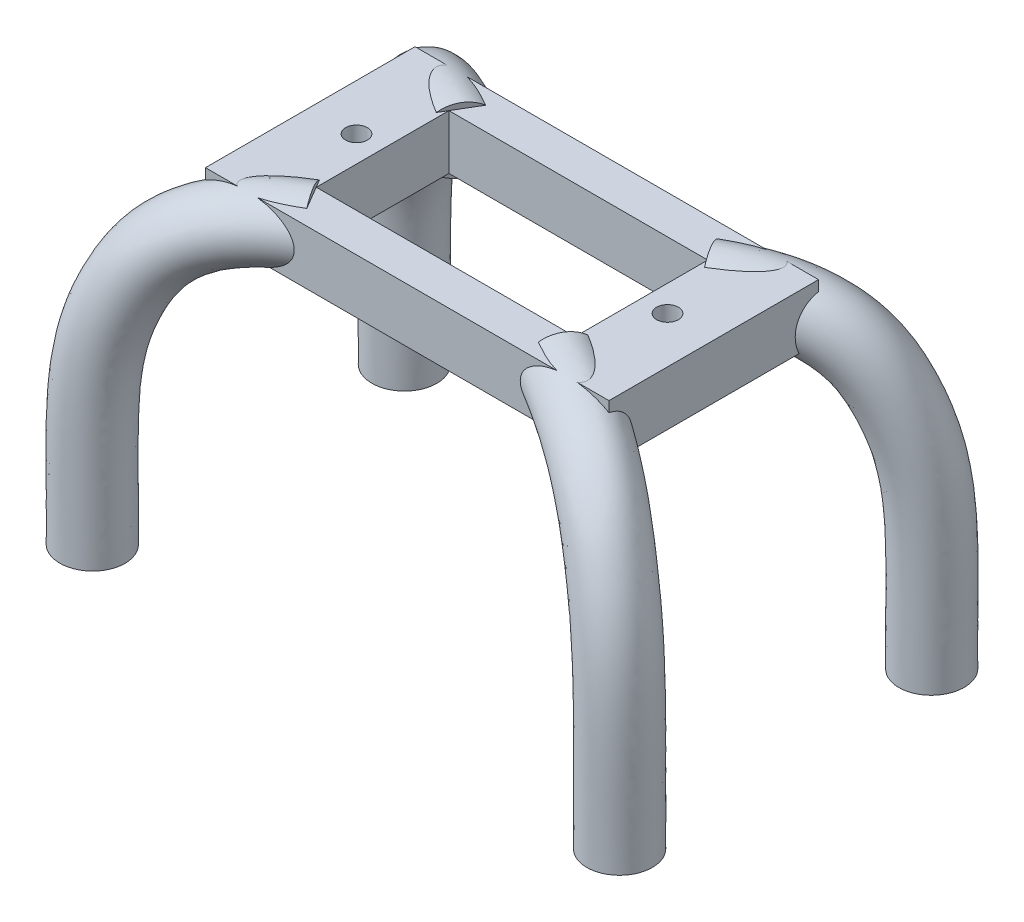
SolidWorks part; units mm, degrees
ref_plane "前视基准面" through (0, 0, 0) normal (0, 0, 1) x (1, 0, 0)
ref_plane "上视基准面" through (0, 0, 0) normal (0, 1, 0) x (1, 0, 0)
ref_plane "右视基准面" through (0, 0, 0) normal (1, 0, 0) x (0, 0, -1)
sketch "草图1" plane through (0, 0, 0) normal (0, 1, 0) x (1, 0, 0)
  line L0 (-5.8, 0) -> (-5.8, 12.535) construction
  line L1 (6.1, -6.1) -> (-17.7, -6.1)
  line L2 (6.1, -6.1) -> (6.1, 6.1)
  line L3 (6.1, 6.1) -> (-17.7, 6.1)
  line L4 (-17.7, -6.1) -> (-17.7, 6.1)
  line L5 (6.1, -6.1) -> (-17.7, 6.1) construction
  line L6 (6.1, 6.1) -> (-17.7, -6.1) construction
  line L7 (12.7533, -9.6358) -> (-24.3533, -9.6358)
  line L8 (12.7533, -9.6358) -> (12.7533, 9.6358)
  line L9 (12.7533, 9.6358) -> (-24.3533, 9.6358)
  line L10 (-24.3533, -9.6358) -> (-24.3533, 9.6358)
  line L11 (12.7533, -9.6358) -> (-24.3533, 9.6358) construction
  line L12 (12.7533, 9.6358) -> (-24.3533, -9.6358) construction
  line L13 (-20.1, 0) -> (-5.8, 0) construction
  circle A0 centre (-20.1, 0) radius 1
  circle A2 centre (8.5, 0) radius 1
  circle A3 centre (0, 0) radius 6.1 construction
  point P0 (-5.8, 0)
  point P6 (-5.8, 0)
  dimension "D4" = 2
  dimension "D1" = 23.8
  dimension "D2" = 12.2
  dimension "D3" = 14.3
extrude "凸台-拉伸1" add sketch "草图1" along normal blind 5
ref_plane "基准面3" through (-5.8, 0, 0) normal (1, 0, 0) x (0, 0, -1)
ref_axis "基准轴1" through (-5.8, 5.25, 0) along (0, -1, 0)
ref_plane "基准面2" through (-1.5042, 0, 2.542) normal (-0.5093, 0, 0.8606) x (0, -1, 0)
sketch "草图2" plane through (-1.5042, 0, 2.542) normal (0.5093, 0, -0.8606) x (-0.8606, 0, -0.5093)
  line L1 (25.8659, 5) -> (25.8659, 0) construction
  line L4 (4.9915, -1.05) -> (4.9915, 8.4021) construction
  line L5 (-8.3562, 5) -> (-8.3562, 0) construction
  line L6 (-8.3562, 5) -> (-8.3562, 0) construction
  line L7 (20.4583, 2.5) -> (-20.4583, 2.5) construction
  line L9 (4.9915, 5.25) -> (4.9915, -0.25) construction
  spline S0 degree 3 poles (-8.3562, 2.5) (-16.3708, 2.496) (-24.1193, -7.0947) (-23.1167, -15.0942) (-23.1865, -25.5) knots 0 0 0 0 0.354063 1 1 1 1
  point P3 (25.8659, 2.5)
  dimension "D1" = 28.178
  dimension "D2" = 28
sweep "扫描1" add path "草图2" circular profile diameter 6 parameters "D3"=6
sketch "草图35" plane through (0.148, -25.6542, 0.0876) normal (0.0058, -1, 0.0034) x (1, 0.0058, 0)
  circle A0 centre (18.3026, 14.263) radius 1.475
  circle A1 centre (18.3026, 14.263) radius 3 construction
  circle A2 centre (18.3026, 14.263) radius 3 construction
  dimension "D1" = 2.95
extrude "切除-拉伸1" cut sketch "草图35" against normal blind 6
mirror "镜向1" about plane through (0, 0, 0) normal (0, 0, 1) of "切除-拉伸1", "扫描1"
mirror "镜向2" about plane through (-5.8, 0, 0) normal (1, 0, 0) of "镜向1"
sketch "草图36" plane through (0, 5, 0) normal (0, 1, 0) x (1, 0, 0)
  line L0 (-24.1533, -9.6358) -> (12.9533, -9.6358) construction
  line L1 (30, -20) -> (-30, -20)
  line L2 (30, -20) -> (30, 20)
  line L3 (30, 20) -> (-30, 20)
  line L4 (-30, -20) -> (-30, 20)
  line L5 (30, -20) -> (-30, 20) construction
  line L6 (30, 20) -> (-30, -20) construction
  line L7 (12.9533, -9.6358) -> (12.9533, 9.6358) construction
  line L8 (12.9533, 9.6358) -> (-24.1533, 9.6358) construction
  line L9 (-24.1533, 9.6358) -> (-24.1533, -9.6358) construction
  line L10 (-24.1533, -9.6358) -> (12.9533, -9.6358)
  line L11 (12.9533, -9.6358) -> (12.9533, 9.6358)
  line L12 (12.9533, 9.6358) -> (-24.1533, 9.6358)
  line L13 (-24.1533, 9.6358) -> (-24.1533, -9.6358)
  point P0 (0, 0)
  dimension "D1" = 40
  dimension "D2" = 60
extrude "凸台-拉伸2" [suppressed] add sketch "草图36" against normal blind 5
sketch "草图45" [suppressed] plane through (0, 0, 0) normal (0, -1, 0) x (1, 0, 0)
  line L0 (30, -20) -> (-30, -20) construction
  line L1 (30, 20) -> (30, -20) construction
  line L2 (-30, 20) -> (30, 20) construction
  line L3 (-30, -20) -> (-30, 20) construction
  line L4 (30, -20) -> (-30, -20)
  line L5 (30, 20) -> (30, -20)
  line L6 (-30, 20) -> (30, 20)
  line L7 (-30, -20) -> (-30, 20)
  line L9 (27, -17) -> (-27, -17)
  line L10 (27, -17) -> (27, 17)
  line L11 (27, 17) -> (-27, 17)
  line L12 (-27, -17) -> (-27, 17)
  line L13 (27, -17) -> (-27, 17) construction
  line L14 (27, 17) -> (-27, -17) construction
  point P3 (0, 0)
  dimension "D1" = 3
  dimension "D2" = 3
extrude "凸台-拉伸3" [suppressed] add sketch "草图45" along normal blind 30
